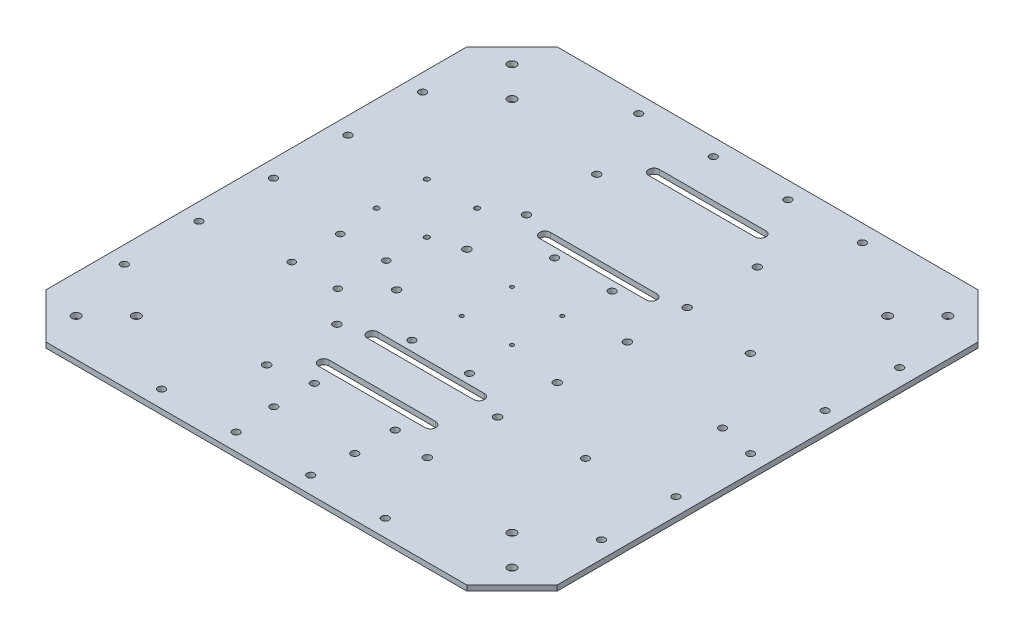
SolidWorks part; units mm, degrees
ref_plane "Front Plane" through (0, 0, 0) normal (0, 0, 1) x (1, 0, 0)
ref_plane "Top Plane" through (0, 0, 0) normal (0, 1, 0) x (1, 0, 0)
ref_plane "Right Plane" through (0, 0, 0) normal (1, 0, 0) x (0, 0, -1)
sketch "Sketch1" plane through (0, 0, 0) normal (0, 1, 0) x (1, 0, 0)
  line L0 (-121.2861, 45.3182) -> (-94.3453, 72.259)
  line L1 (-121.2861, 72.259) -> (183.5139, 72.259)
  line L2 (-121.2861, 72.259) -> (-121.2861, -232.541)
  line L3 (-121.2861, -232.541) -> (183.5139, -232.541)
  line L4 (183.5139, 72.259) -> (183.5139, -232.541)
  line L5 (31.1139, 95.069) -> (31.1139, -294.9418) construction
  line L6 (-146.0448, -80.141) -> (218.038, -80.141) construction
  line L7 (183.5139, 45.3182) -> (156.5732, 72.259)
  line L8 (183.5139, -205.6003) -> (156.5732, -232.541)
  line L9 (-121.2861, -205.6003) -> (-94.3453, -232.541)
  point P8 (31.1139, 72.259)
  point P11 (-121.2861, -80.141)
  dimension "D1" = 304.8
  dimension "D2" = 304.8
  dimension "D3" = 45
  dimension "D4" = 38.1
extrude "Boss-Extrude1" add sketch "Sketch1" along normal blind 3.175 contours L2 L9 L3 L8 L4 L7 L1 L0 region at (31.1139, 0, 80.141)
sketch "Sketch2" plane through (0, 3.175, 0) normal (0, 1, 0) x (1, 0, 0)
  line L0 (31.1139, 72.259) -> (31.1139, -287.8465) construction
  line L1 (-94.3453, 72.259) -> (156.5732, 72.259) construction
  line L2 (183.5139, -80.141) -> (-158.2106, -80.141) construction
  line L3 (183.5139, 45.3182) -> (183.5139, -205.6003) construction
  circle A0 centre (13.8419, -37.469) radius 2.159
  circle A1 centre (48.1319, -37.469) radius 2.159
  circle A2 centre (13.8419, -122.559) radius 2.159
  circle A3 centre (48.1319, -122.559) radius 2.159
  dimension "D5" = 4.318
  dimension "D6" = 4.318
  dimension "D7" = 4.318
  dimension "D8" = 4.318
  dimension "D1" = 17.272
  dimension "D2" = 34.29
  dimension "D3" = 85.09
  dimension "D4" = 42.672
extrude "Cut-Extrude1" cut sketch "Sketch2" against normal through all
sketch "Sketch4" plane through (0, 3.175, 0) normal (0, 1, 0) x (1, 0, 0)
  line L0 (-0.6361, 36.294) -> (62.8639, 36.294) construction
  line L1 (-0.6361, 39.469) -> (62.8639, 39.469)
  line L2 (-0.6361, 33.119) -> (62.8639, 33.119)
  line L3 (-0.6361, -28.706) -> (62.8639, -28.706) construction
  line L4 (-0.6361, -25.531) -> (62.8639, -25.531)
  line L5 (-0.6361, -31.881) -> (62.8639, -31.881)
  line L6 (31.1139, 72.259) -> (31.1139, -65.9651) construction
  line L7 (-94.3453, 72.259) -> (156.5732, 72.259) construction
  line L8 (-121.2861, -80.141) -> (257.7387, -80.141) construction
  line L9 (-121.2861, 45.3182) -> (-121.2861, -205.6003) construction
  line L10 (31.1139, -232.541) -> (31.1139, -94.317) construction
  line L11 (-0.6361, -131.576) -> (62.8639, -131.576) construction
  line L12 (-0.6361, -128.401) -> (62.8639, -128.401)
  line L13 (-0.6361, -134.751) -> (62.8639, -134.751)
  line L14 (-0.6361, -160.576) -> (62.8639, -160.576) construction
  line L15 (-0.6361, -157.401) -> (62.8639, -157.401)
  line L16 (-0.6361, -163.751) -> (62.8639, -163.751)
  arc A0 (-0.6361, 39.469) -> (-0.6361, 33.119) centre (-0.6361, 36.294) ccw
  arc A1 (62.8639, 33.119) -> (62.8639, 39.469) centre (62.8639, 36.294) ccw
  arc A2 (-0.6361, -25.531) -> (-0.6361, -31.881) centre (-0.6361, -28.706) ccw
  arc A3 (62.8639, -31.881) -> (62.8639, -25.531) centre (62.8639, -28.706) ccw
  arc A5 (-0.6361, -128.401) -> (-0.6361, -134.751) centre (-0.6361, -131.576) ccw
  arc A6 (62.8639, -134.751) -> (62.8639, -128.401) centre (62.8639, -131.576) ccw
  arc A7 (-0.6361, -157.401) -> (-0.6361, -163.751) centre (-0.6361, -160.576) ccw
  arc A8 (62.8639, -163.751) -> (62.8639, -157.401) centre (62.8639, -160.576) ccw
  point P2 (31.1139, 36.294)
  point P7 (31.1139, -28.706)
  point P28 (31.1139, -131.576)
  point P33 (31.1139, -160.576)
  dimension "D1" = 63.5
  dimension "D2" = 63.5
  dimension "D3" = 6.35
  dimension "D4" = 6.35
  dimension "D5" = 65
  dimension "D6" = 48.26
  dimension "D7" = 63.5
  dimension "D8" = 63.5
  dimension "D9" = 6.35
  dimension "D10" = 6.35
  dimension "D11" = 29
  dimension "D12" = 48.26
extrude "Cut-Extrude2" cut sketch "Sketch4" against normal through all
sketch "Sketch7" plane through (0, 3.175, 0) normal (0, 1, 0) x (1, 0, 0)
  line L0 (-49.9121, 53.9596) -> (-49.9121, -59.6418) construction
  line L1 (-121.2861, -80.141) -> (183.5139, -80.141) construction
  line L2 (-121.2861, 45.3182) -> (-121.2861, -205.6003) construction
  line L3 (183.5139, 45.3182) -> (183.5139, -205.6003) construction
  line L4 (31.1139, 72.259) -> (31.1139, -252.674) construction
  line L5 (-94.3453, 72.259) -> (156.5732, 72.259) construction
  circle A0 centre (-34.9261, -34.929) radius 1.524
  circle A1 centre (-34.9261, -64.901) radius 1.524
  circle A2 centre (-64.8981, -64.901) radius 1.524
  circle A3 centre (-64.8981, -34.929) radius 1.524
  dimension "D1" = 3.048
  dimension "D2" = 14.986
  dimension "D4" = 29.972
  dimension "D3" = 3.048
  dimension "D5" = 15.24
  dimension "D6" = 66.04
  dimension "D7" = 14.986
extrude "Cut-Extrude3" cut sketch "Sketch7" against normal through all
sketch "Sketch8" plane through (0, 3.175, 0) normal (0, 1, 0) x (1, 0, 0)
  line L0 (-94.3453, -232.541) -> (156.5732, -232.541) construction
  line L1 (183.5139, 45.3182) -> (183.5139, -205.6003) construction
  circle A0 centre (73.0239, -207.649) radius 1.524
  circle A1 centre (73.0239, -177.169) radius 1.524
  circle A2 centre (96.8999, -207.649) radius 1.524
  circle A3 centre (96.8999, -177.169) radius 1.524
  dimension "D1" = 3.048
  dimension "D2" = 30.48
  dimension "D3" = 23.876
  dimension "D4" = 24.892
  dimension "D5" = 86.614
extrude "Cut-Extrude4" [suppressed] cut sketch "Sketch8" against normal through all and the other way through all
sketch "Sketch10" plane through (0, 0, 0) normal (0, -1, 0) x (1, 0, 0)
  line L0 (-94.3453, 232.541) -> (156.5732, 232.541) construction
  line L1 (31.1139, 232.541) -> (31.1139, 128.7119) construction
  line L2 (-0.6361, 163.751) -> (62.8639, 163.751) construction
  circle A0 centre (6.9839, 198.041) radius 2.159
  circle A1 centre (55.2439, 198.041) radius 2.159
  circle A2 centre (6.9839, 173.911) radius 2.159
  circle A3 centre (55.2439, 173.911) radius 2.159
  dimension "D1" = 4.318
  dimension "D2" = 48.26
  dimension "D4" = 10.16
  dimension "D6" = 4.318
  dimension "D7" = 4.318
  dimension "D8" = 4.318
  dimension "D3" = 24.13
  dimension "D5" = 24.13
extrude "Cut-Extrude6" cut sketch "Sketch10" against normal through all
sketch "Sketch9" plane through (0, 0, 0) normal (0, -1, 0) x (-1, 0, 0)
  line L1 (121.2861, -80.141) -> (-327.4314, -80.141) construction
  line L2 (48.6421, -47.3693) -> (48.6421, -130.2963) construction
  line L3 (-31.1139, 72.259) -> (-31.1139, -331.7119) construction
  line L4 (94.3453, 72.259) -> (-156.5732, 72.259) construction
  line L7 (121.2861, 45.3182) -> (121.2861, -205.6003) construction
  circle A0 centre (62.3581, -117.987) radius 2.032
  circle A1 centre (34.9261, -117.987) radius 2.032
  circle A2 centre (62.3581, -89.031) radius 2.032
  circle A3 centre (34.9261, -89.031) radius 2.032
  dimension "D1" = 4.064
  dimension "D9" = 4.064
  dimension "D2" = 66.04
  dimension "D3" = 28.956
  dimension "D4" = 8.89
  dimension "D8" = 13.716
extrude "Cut-Extrude5" cut sketch "Sketch9" against normal through all
sketch "Sketch13" plane through (0, 0, 0) normal (0, -1, 0) x (1, 0, 0)
  line L0 (31.1139, -72.259) -> (31.1139, 261.4711) construction
  line L1 (-94.3453, -72.259) -> (156.5732, -72.259) construction
  line L2 (-121.2861, 80.141) -> (239.2508, 80.141) construction
  line L3 (-121.2861, -45.3182) -> (-121.2861, 205.6003) construction
  circle A0 centre (16.1139, 95.141) radius 1.1
  circle A1 centre (16.1139, 65.141) radius 1.1
  circle A2 centre (46.1139, 65.141) radius 1.1
  circle A3 centre (46.1139, 95.141) radius 1.1
  dimension "D1" = 2.2
  dimension "D2" = 2.2
  dimension "D3" = 30
  dimension "D4" = 15
  dimension "D5" = 15
extrude "Cut-Extrude8" cut sketch "Sketch13" against normal through all
sketch "Sketch14" plane through (0, 0, 0) normal (0, -1, 0) x (1, 0, 0)
  line L0 (31.1139, 232.541) -> (31.1139, -154.5354) construction
  line L1 (-94.3453, 232.541) -> (156.5732, 232.541) construction
  line L2 (-121.2861, 80.141) -> (331.9066, 80.141) construction
  line L3 (-121.2861, -45.3182) -> (-121.2861, 205.6003) construction
  line L4 (-121.2861, 205.6003) -> (-94.3453, 232.541) construction
  line L5 (-224.559, -175.5319) -> (286.7869, 335.814) construction
  line L6 (-224.559, -175.5319) -> (286.7869, -175.5319) construction
  line L7 (-224.559, -175.5319) -> (-224.559, 335.814) construction
  line L8 (-121.2861, 205.6003) -> (-94.3453, 232.541) construction
  line L9 (-107.8157, 219.0706) -> (-48.5429, 159.7979) construction
  line L10 (-224.559, 335.814) -> (286.7869, 335.814) construction
  line L11 (286.7869, -175.5319) -> (286.7869, 335.814) construction
  line L12 (286.7869, -175.5319) -> (-224.559, 335.814) construction
  line L14 (-121.2861, -45.3182) -> (-94.3453, -72.259) construction
  line L21 (-224.559, -175.5319) -> (-107.8157, -58.7886) construction
  line L22 (170.0436, -58.7886) -> (286.7869, -175.5319) construction
  line L23 (183.5139, -45.3182) -> (156.5732, -72.259) construction
  line L24 (170.0436, 219.0706) -> (286.7869, 335.814) construction
  line L25 (183.5139, 205.6003) -> (156.5732, 232.541) construction
  line L26 (-224.559, 335.814) -> (-107.8157, 219.0706) construction
  circle A1 centre (-98.8354, 210.0904) radius 2.54
  circle A3 centre (-80.8749, 192.1299) radius 2.54
  circle A4 centre (143.1028, 192.1299) radius 2.54
  circle A7 centre (161.0633, 210.0904) radius 2.54
  circle A8 centre (-98.8354, -49.8083) radius 2.54
  circle A11 centre (-80.8749, -31.8478) radius 2.54
  circle A14 centre (161.0633, -49.8083) radius 2.54
  circle A15 centre (143.1028, -31.8478) radius 2.54
  point P8 (31.1139, 80.141)
  point P30 (286.7869, 80.141)
  point P33 (-107.8157, -58.7886)
  point P36 (31.1139, -175.5319)
  dimension "D3" = 5.08
  dimension "D6" = 5.08
  dimension "D1" = 12.7
  dimension "D2" = 165.1
  dimension "D9" = 25.4
extrude "Cut-Extrude9" cut sketch "Sketch14" against normal through all
sketch "Sketch15" plane through (0, 0, 0) normal (0, -1, 0) x (1, 0, 0)
  line L0 (31.1139, 232.541) -> (31.1139, 125.875) construction
  line L1 (-94.3453, 232.541) -> (156.5732, 232.541) construction
  line L2 (-121.2861, 80.141) -> (75.4631, 80.141) construction
  line L3 (-121.2861, -45.3182) -> (-121.2861, 205.6003) construction
  circle A0 centre (8.8889, 222.381) radius 2.159
  circle A1 centre (-35.5611, 222.381) radius 2.159
  circle A2 centre (-111.1261, 80.141) radius 2.159
  circle A3 centre (-111.1261, 124.591) radius 2.159
  circle A4 centre (-111.1261, 169.041) radius 2.159
  circle A5 centre (173.3539, 169.041) radius 2.159
  circle A6 centre (173.3539, 124.591) radius 2.159
  circle A7 centre (173.3539, 80.141) radius 2.159
  circle A8 centre (97.7889, 222.381) radius 2.159
  circle A9 centre (53.3389, 222.381) radius 2.159
  circle A10 centre (53.3389, -62.099) radius 2.159
  circle A11 centre (97.7889, -62.099) radius 2.159
  circle A12 centre (173.3539, 35.691) radius 2.159
  circle A13 centre (173.3539, -8.759) radius 2.159
  circle A14 centre (-111.1261, -8.759) radius 2.159
  circle A15 centre (-111.1261, 35.691) radius 2.159
  circle A16 centre (-35.5611, -62.099) radius 2.159
  circle A17 centre (8.8889, -62.099) radius 2.159
  dimension "D3" = 4.318
  dimension "D4" = 4.318
  dimension "D8" = 4.318
  dimension "D9" = 4.318
  dimension "D10" = 4.318
  dimension "D1" = 22.225
  dimension "D2" = 44.45
  dimension "D5" = 10.16
  dimension "D6" = 44.45
  dimension "D7" = 44.45
  dimension "D11" = 10.16
extrude "Cut-Extrude10" cut sketch "Sketch15" against normal through all
sketch "Sketch16" plane through (0, 0, 0) normal (0, -1, 0) x (-1, 0, 0)
  line L0 (-31.1139, 72.259) -> (-31.1139, -323.0503) construction
  line L1 (-101.2179, -121.924) -> (-141.8579, -121.924)
  line L2 (-101.2179, -121.924) -> (-101.2179, -38.358)
  line L3 (-101.2179, -38.358) -> (-141.8579, -38.358)
  line L4 (-141.8579, -121.924) -> (-141.8579, -38.358)
  line L6 (94.3453, 72.259) -> (-156.5732, 72.259) construction
  line L7 (121.2861, -80.141) -> (-312.3855, -80.141) construction
  line L8 (121.2861, 45.3182) -> (121.2861, -205.6003) construction
  circle A0 centre (-126.6179, -131.83) radius 2.159
  circle A1 centre (-121.5379, -28.452) radius 2.159
  circle A2 centre (-151.7639, -75.274) radius 2.159
  point P18 (-141.8579, -80.141)
  dimension "D3" = 9.906
  dimension "D4" = 9.906
  dimension "D5" = 9.906
  dimension "D6" = 15.24
  dimension "D7" = 20.32
  dimension "D8" = 46.65
  dimension "D9" = 4.318
  dimension "D10" = 4.318
  dimension "D11" = 4.318
  dimension "D1" = 83.566
  dimension "D2" = 40.64
  dimension "D12" = 120.65
  dimension "D13" = 0
extrude "Cut-Extrude11" cut sketch "Sketch16" against normal through all contours A2 | A0 | A1
sketch "Sketch17" plane through (0, 3.175, 0) normal (0, 1, 0) x (1, 0, 0)
  line L2 (31.1139, 72.259) -> (31.1139, -395.818) construction
  line L3 (-94.3453, 72.259) -> (156.5732, 72.259) construction
  line L4 (183.5139, -80.141) -> (-127.1454, -80.141) construction
  line L5 (183.5139, 45.3182) -> (183.5139, -205.6003) construction
  circle A12 centre (78.9929, -178.566) radius 2.2225
  circle A13 centre (-16.7651, -178.566) radius 2.2225
  circle A14 centre (78.9929, -136.656) radius 2.2225
  circle A15 centre (-16.7651, -136.656) radius 2.2225
  circle A16 centre (78.9929, -101.096) radius 2.2225
  circle A17 centre (-16.7651, -101.096) radius 2.2225
  circle A18 centre (78.9929, -59.186) radius 2.2225
  circle A19 centre (-16.7651, -59.186) radius 2.2225
  circle A20 centre (78.9929, -23.626) radius 2.2225
  circle A21 centre (-16.7651, -23.626) radius 2.2225
  circle A22 centre (78.9929, 18.284) radius 2.2225
  circle A23 centre (-16.7651, 18.284) radius 2.2225
  circle A24 centre (-16.7651, 18.284) radius 2.2225
  circle A25 centre (78.9929, 18.284) radius 2.2225
  circle A26 centre (-16.7651, -23.626) radius 2.2225
  circle A27 centre (78.9929, -23.626) radius 2.2225
  circle A28 centre (-16.7651, -59.186) radius 2.2225
  circle A29 centre (78.9929, -59.186) radius 2.2225
  circle A30 centre (-16.7651, -101.096) radius 2.2225
  circle A31 centre (78.9929, -101.096) radius 2.2225
  circle A32 centre (-16.7651, -136.656) radius 2.2225
  circle A33 centre (78.9929, -136.656) radius 2.2225
  circle A34 centre (-16.7651, -178.566) radius 2.2225
  dimension "D1" = 4.445
  dimension "D2" = 4.445
  dimension "D3" = 4.445
  dimension "D4" = 4.445
  dimension "D5" = 4.445
  dimension "D6" = 4.445
  dimension "D7" = 4.445
  dimension "D8" = 4.445
  dimension "D9" = 4.445
  dimension "D10" = 4.445
  dimension "D11" = 4.445
  dimension "D12" = 4.445
  dimension "D25" = 56.515
  dimension "D24" = 56.515
  dimension "D13" = 95.758
  dimension "D14" = 41.91
  dimension "D15" = 95.758
  dimension "D16" = 41.91
  dimension "D17" = 95.758
  dimension "D18" = 41.91
  dimension "D19" = 47.879
  dimension "D20" = 47.879
  dimension "D21" = 47.879
  dimension "D22" = 20.955
extrude "Cut-Extrude13" cut sketch "Sketch17" against normal through all contours A23 | A22 | A20 | A21 | A18 | A19 | A17 | A16 | A12 | A14 | A15 | A13
